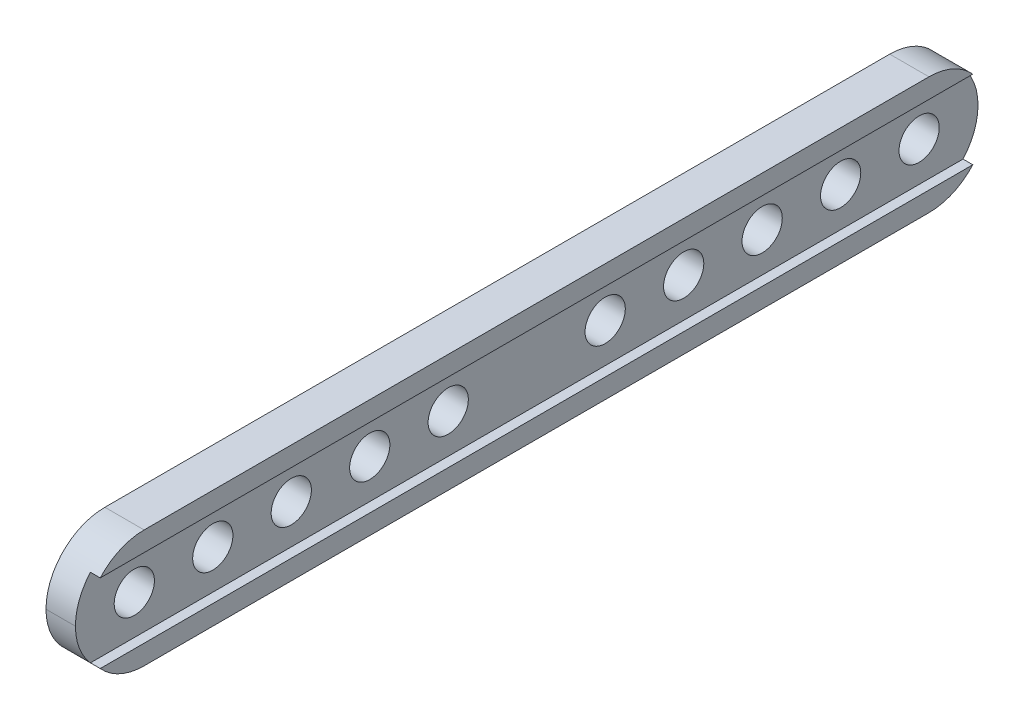
SolidWorks part; units mm, degrees
ref_plane "Front Plane" through (0, 0, 0) normal (0, 0, 1) x (1, 0, 0)
ref_plane "Top Plane" through (0, 0, 0) normal (0, 1, 0) x (1, 0, 0)
ref_plane "Right Plane" through (0, 0, 0) normal (1, 0, 0) x (0, 0, -1)
sketch "Sketch1" plane through (0, 0, 0) normal (0, 0, 1) x (1, 0, 0)
  line L0 (3, 6) -> (0, 6) construction
  line L1 (0, 0) -> (4, 0)
  line L2 (0, 0) -> (0, 12)
  line L3 (0, 12) -> (4, 12)
  line L4 (4, 0) -> (4, 2)
  line L5 (4, 10) -> (3, 10)
  line L7 (4, 2) -> (3, 2)
  line L8 (3, 10) -> (3, 2)
  line L9 (4, 10) -> (4, 12)
  dimension "D1" = 4
  dimension "D2" = 12
  dimension "D3" = 8
  dimension "D4" = 1
extrude "Boss-Extrude1" add sketch "Sketch1" against normal blind 92
ref_plane "Plane1" through (0, 0, -46) normal (0, 0, 1) x (1, 0, 0)
fillet "Fillet1" radius 6 4 edges at (2, 12, 0) (2, 0, 0) (2, 0, -92) (2, 12, -92)
sketch "Sketch2" plane through (0, 0, 0) normal (-1, 0, 0) x (0, 0, 1)
  circle A0 centre (-86, 6) radius 2.05
  dimension "D1" = 4.1
extrude "Cut-Extrude1" cut sketch "Sketch2" against normal through all
pattern_linear "LPattern1" count 5 spacing 8 along (0, 0, 1) of "Cut-Extrude1"
mirror "Mirror1" about plane through (0, 0, -46) normal (0, 0, 1) of "LPattern1", "Cut-Extrude1"
